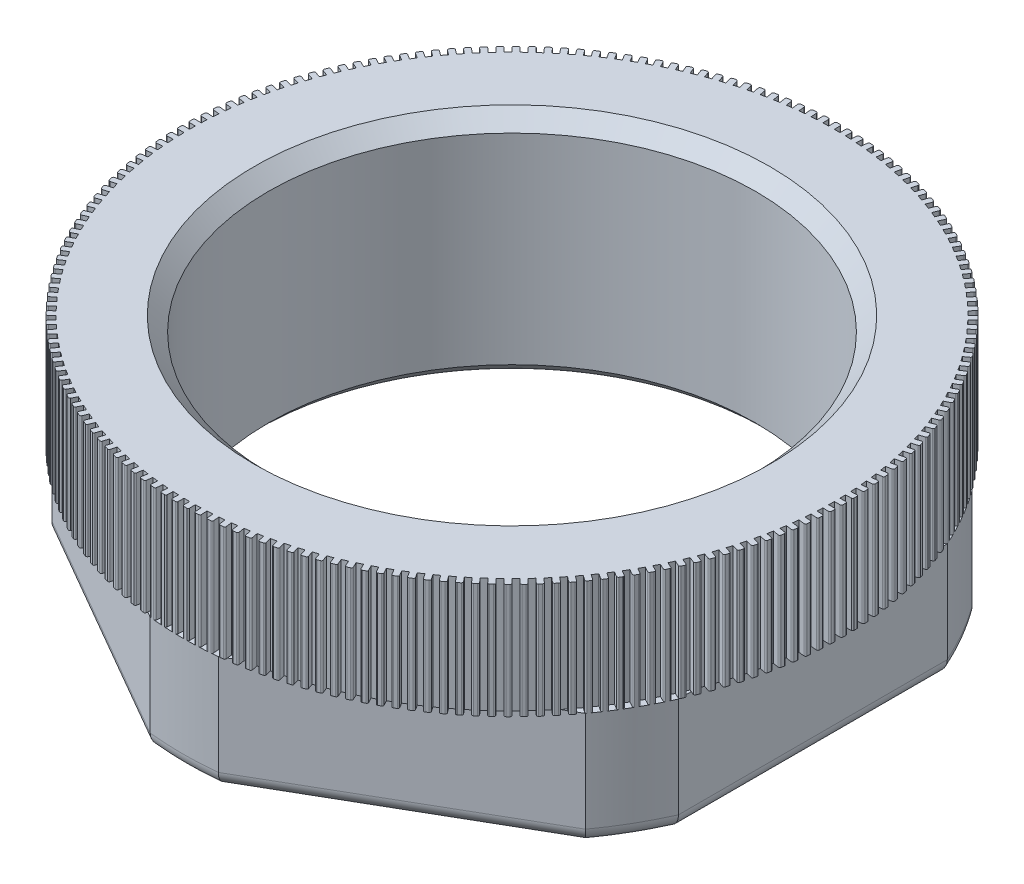
SolidWorks part; units mm, degrees
ref_plane "Front Plane" through (0, 0, 0) normal (0, 0, 1) x (1, 0, 0)
ref_plane "Top Plane" through (0, 0, 0) normal (0, 1, 0) x (1, 0, 0)
ref_plane "Right Plane" through (0, 0, 0) normal (1, 0, 0) x (0, 0, -1)
sketch "Sketch1" plane through (0, 0, 0) normal (0, 1, 0) x (1, 0, 0)
  line L1 (0, -12.1244) -> (10.5, -6.0622)
  line L2 (10.5, -6.0622) -> (10.5, 6.0622)
  line L3 (10.5, 6.0622) -> (0, 12.1244)
  line L4 (0, 12.1244) -> (-10.5, 6.0622)
  line L5 (-10.5, 6.0622) -> (-10.5, -6.0622)
  line L6 (-10.5, -6.0622) -> (0, -12.1244)
  circle A0 centre (0, 0) radius 10.5 construction
  circle A1 centre (0, 0) radius 8.5
  dimension "D2" = 17
  dimension "D1" = 21
extrude "Boss-Extrude1" add sketch "Sketch1" along normal blind 4
sketch "Sketch2" plane through (0, 4, 0) normal (0, 1, 0) x (1, 0, 0)
  circle A0 centre (0, 0) radius 11.5
  circle A1 centre (0, 0) radius 8.5 construction
  circle A2 centre (0, 0) radius 8.5
  dimension "D1" = 23
extrude "Boss-Extrude2" add sketch "Sketch2" along normal blind 4
sketch "Sketch3" plane through (0, 8, 0) normal (0, 1, 0) x (1, 0, 0)
  circle A0 centre (0, 0) radius 11.5 construction
  circle A1 centre (0, 0) radius 11.5
extrude "Cut-Extrude1" cut sketch "Sketch3" against normal through all flip side to cut
sketch "Sketch4" plane through (0, 8, 0) normal (0, 1, 0) x (1, 0, 0)
  line L0 (0, 11.25) -> (0, 11.4499)
  line L1 (0.1963, 11.2483) -> (0.1998, 11.4481)
  arc A1 (0.1963, 11.2483) -> (0, 11.25) centre (0, 0) ccw
  circle A4 centre (0, 0) radius 11.5 construction
  arc A5 (0, 11.4499) -> (-0.0502, 11.4999) centre (-0.05, 11.4499) ccw
  arc A6 (0.2509, 11.4973) -> (0.1998, 11.4481) centre (0.2498, 11.4473) ccw
  arc A7 (0.2509, 11.4973) -> (-0.0502, 11.4999) centre (0, 0) ccw
  dimension "D2" = 22.5
  dimension "D3" = 0.05
  dimension "D4" = 0.05
  dimension "D1" = 1
extrude "Cut-Extrude2" cut sketch "Sketch4" against normal blind 4
pattern_circular "CirPattern1" count 180 over 360 about axis through (0, 4, 0) along (0, -1, 0) of "Cut-Extrude2"
chamfer "Chamfer1" distance 0.5 angle 45 2 edges at (0, 8, 8.5) (0, 0, 8.5)
fillet "Fillet1" radius 0.5 13 edges at (10.5, 0, 0) (9.9593, 0, -5.75) (5.25, 0, -9.0933) (0, 0, -11.5) (-5.25, 0, -9.0933) (-9.9593, 0, -5.75) (-10.5, 0, 0) (-9.9593, 0, 5.75) (-5.25, 0, 9.0933) (0, 0, 11.5) (5.25, 0, 9.0933) (9.9593, 0, 5.75) (0, 0, 9)
